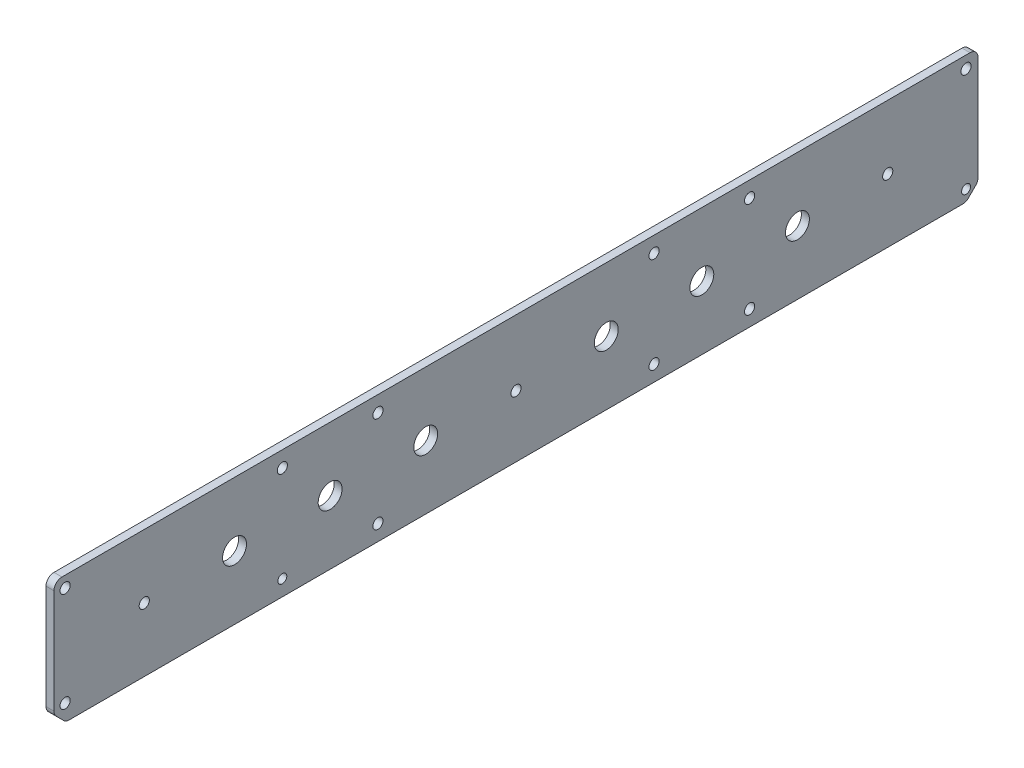
SolidWorks part; units mm, degrees
ref_plane "Front Plane" through (0, 0, 0) normal (0, 0, 1) x (1, 0, 0)
ref_plane "Top Plane" through (0, 0, 0) normal (0, 1, 0) x (1, 0, 0)
ref_plane "Right Plane" through (0, 0, 0) normal (1, 0, 0) x (0, 0, -1)
sketch "Sketch1" plane through (0, 0, 0) normal (1, 0, 0) x (0, 0, -1)
  line L5 (-184.15, -24.6062) -> (184.15, -24.6062)
  line L6 (-184.15, -24.6062) -> (-184.15, 26.1937)
  line L7 (-184.15, 26.1937) -> (184.15, 26.1937)
  line L8 (184.15, -24.6062) -> (184.15, 26.1937)
  line L9 (-184.15, -24.6062) -> (184.15, 26.1937) construction
  line L10 (-184.15, 26.1937) -> (184.15, -24.6062) construction
  point P0 (0, 0.7937)
  point P6 (0, 0)
  point P8 (0, 9.9746)
  dimension "D1" = 50.8
  dimension "D2" = 368.3
  dimension "D3" = 24.6062
extrude "Boss-Extrude1" add sketch "Sketch1" along normal blind 3.175
chamfer "Chamfer1" distance 4.7625 angle 45 2 edges at (1.5875, -24.6062, -184.15) (1.5875, -24.6062, 184.15)
fillet "Fillet1" radius 3.175 6 edges at (1.5875, -24.6062, 179.3875) (1.5875, -19.8437, 184.15) (1.5875, 26.1937, 184.15) (1.5875, -24.6062, -179.3875) (1.5875, -19.8437, -184.15) (1.5875, 26.1937, -184.15)
sketch "Sketch3" plane through (3.175, 0, 0) normal (1, 0, 0) x (0, 0, -1)
  point P0 (-93.1246, 19.9098)
  point P3 (-55.0246, 19.9098)
  point P6 (-55.0246, -18.3223)
  point P9 (55.0246, -18.3223)
  point P12 (55.0246, 19.9098)
  point P15 (93.1246, 19.9098)
  point P18 (93.1246, -18.3223)
  point P21 (0, 0)
hole_wizard "#8 Clearance Hole1" positions "Sketch3" profile "Sketch4" hole size "#8" standard "ANSI Inch" end condition up to next
sketch "Sketch4" plane through (3.175, 19.9098, 93.1246) normal (0, 1, 0) x (0, 0, -1)
  line L0 (0, 0) -> (0, 3.175)
  line L1 (0, 3.175) -> (2.032, 3.175)
  line L2 (2.032, 3.175) -> (2.032, 0)
  line L5 (2.032, 0) -> (0, 0)
  line L11 (0, -6.35) -> (0, 107.95) construction
  dimension "Thru Hole Dia." = 4.064
  dimension "Thru Hole Depth" = 3.175
sketch "Sketch5" plane through (3.175, 0, 0) normal (1, 0, 0) x (0, 0, -1)
  circle A0 centre (-93.1246, -18.3223) radius 1.778
  circle A1 centre (179.3875, -20.1161) radius 1.778
  circle A2 centre (179.3875, -20.1161) radius 1.651 construction
  dimension "D1" = 3.556
extrude "Cut-Extrude1" cut sketch "Sketch5" against normal through all
sketch "Sketch6" plane through (3.175, 0, 0) normal (1, 0, 0) x (0, 0, -1)
  circle A0 centre (-179.705, 21.7487) radius 2.032
  circle A1 centre (-179.705, -18.0026) radius 2.032
  circle A2 centre (-148.1579, 0.7937) radius 2.032
  circle A3 centre (148.1579, 0.7938) radius 2.032
  circle A4 centre (179.3875, 21.4312) radius 2.032
  circle A5 centre (-148.1579, 0.7937) radius 2.032 construction
  circle A6 centre (-179.705, -18.0026) radius 1.905 construction
  circle A7 centre (-179.705, 21.7487) radius 1.905 construction
  circle A8 centre (148.1579, 0.7938) radius 2.032 construction
  circle A9 centre (179.3875, 21.4312) radius 1.905 construction
  point P10 (-148.7516, -0.8964)
  dimension "D1" = 4.064
extrude "Cut-Extrude2" cut sketch "Sketch6" against normal through all
sketch "Sketch7" plane through (3.175, 0, 0) normal (1, 0, 0) x (0, 0, -1)
  circle A0 centre (-112.1746, 0.7937) radius 4.7625
  circle A1 centre (-74.0746, 0.7938) radius 4.7625
  circle A2 centre (-35.9746, 0.7938) radius 4.7625
  circle A3 centre (35.9746, 0.7937) radius 4.7625
  circle A4 centre (74.0746, 0.7937) radius 4.7625
  circle A5 centre (112.1746, 0.7937) radius 4.7625
  dimension "D1" = 9.525
extrude "Cut-Extrude3" cut sketch "Sketch7" against normal through all
